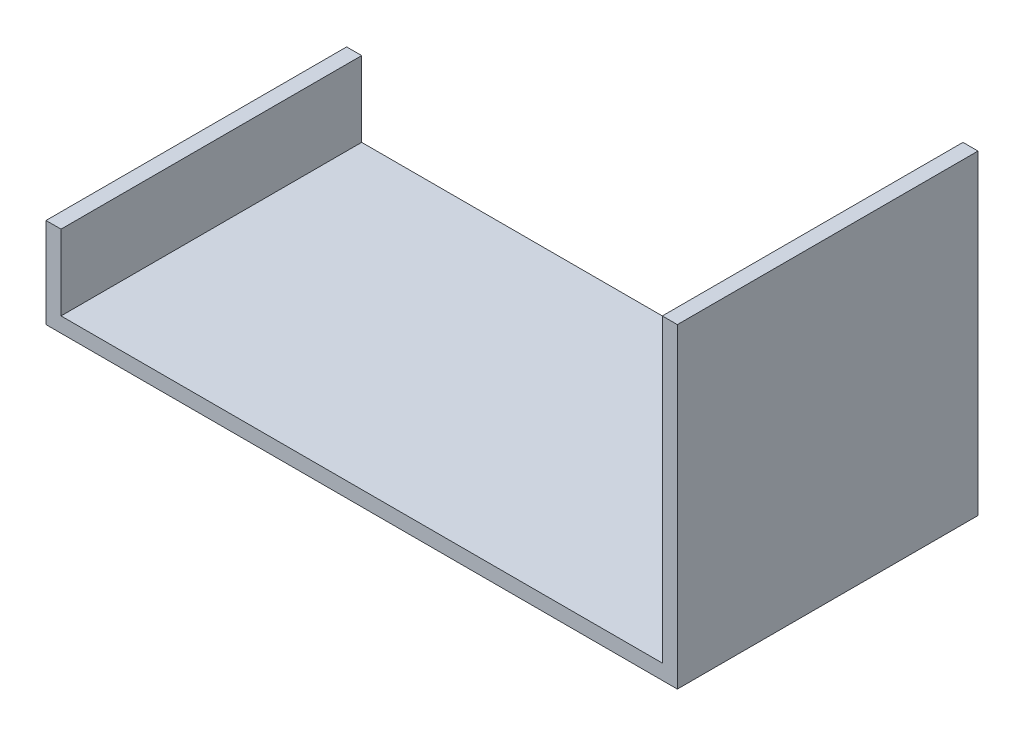
SolidWorks part; units mm, degrees
ref_plane "前视基准面" through (0, 0, 0) normal (0, 0, 1) x (1, 0, 0)
ref_plane "上视基准面" through (0, 0, 0) normal (0, 1, 0) x (1, 0, 0)
ref_plane "右视基准面" through (0, 0, 0) normal (1, 0, 0) x (0, 0, -1)
sketch "草图1" plane through (0, 0, 0) normal (0, 0, 1) x (1, 0, 0)
  line L0 (-46.573, 28.5853) -> (-46.573, 18.5853)
  line L1 (-46.573, 18.5853) -> (33.427, 18.5853)
  line L2 (33.427, 18.5853) -> (33.427, 58.5853)
  line L3 (33.427, 58.5853) -> (35.427, 58.5853)
  line L4 (35.427, 58.5853) -> (35.427, 16.5853)
  line L5 (35.427, 16.5853) -> (-48.573, 16.5853)
  line L6 (-48.573, 16.5853) -> (-48.573, 28.5853)
  line L7 (-48.573, 28.5853) -> (-46.573, 28.5853)
extrude "凸台-拉伸1" add sketch "草图1" along normal blind 40
